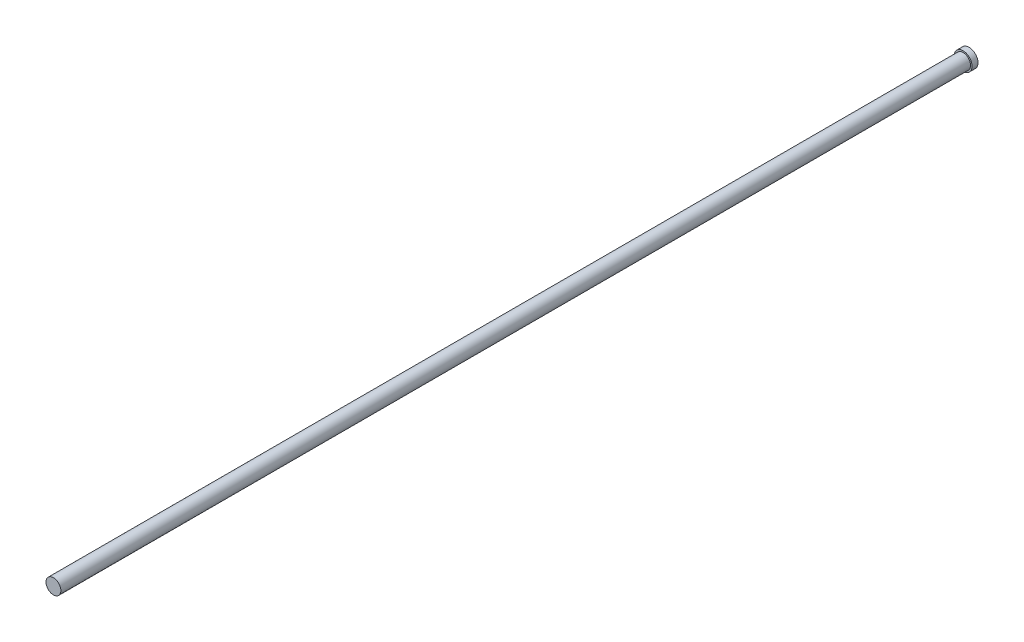
SolidWorks part; units mm, degrees
ref_plane "Front Plane" through (0, 0, 0) normal (0, 0, 1) x (1, 0, 0)
ref_plane "Top Plane" through (0, 0, 0) normal (0, 1, 0) x (1, 0, 0)
ref_plane "Right Plane" through (0, 0, 0) normal (1, 0, 0) x (0, 0, -1)
sketch "Sketch2" plane through (0, 0, 0) normal (0, 0, 1) x (1, 0, 0)
  circle A0 centre (-13.0879, 5.5684) radius 3
  circle A1 centre (-13.0869, 5.5492) radius 2.5
  dimension "D1" = 6
  dimension "D2" = 5
extrude "Boss-Extrude1" add sketch "Sketch2" along normal blind 305 contours A1
extrude "Boss-Extrude2" add sketch "Sketch2<5>" against normal blind 2 contours A0
sketch "Sketch2<5>" plane through (0, 0, 0) normal (0, 0, 1) x (1, 0, 0) same geometry as "Sketch2"
